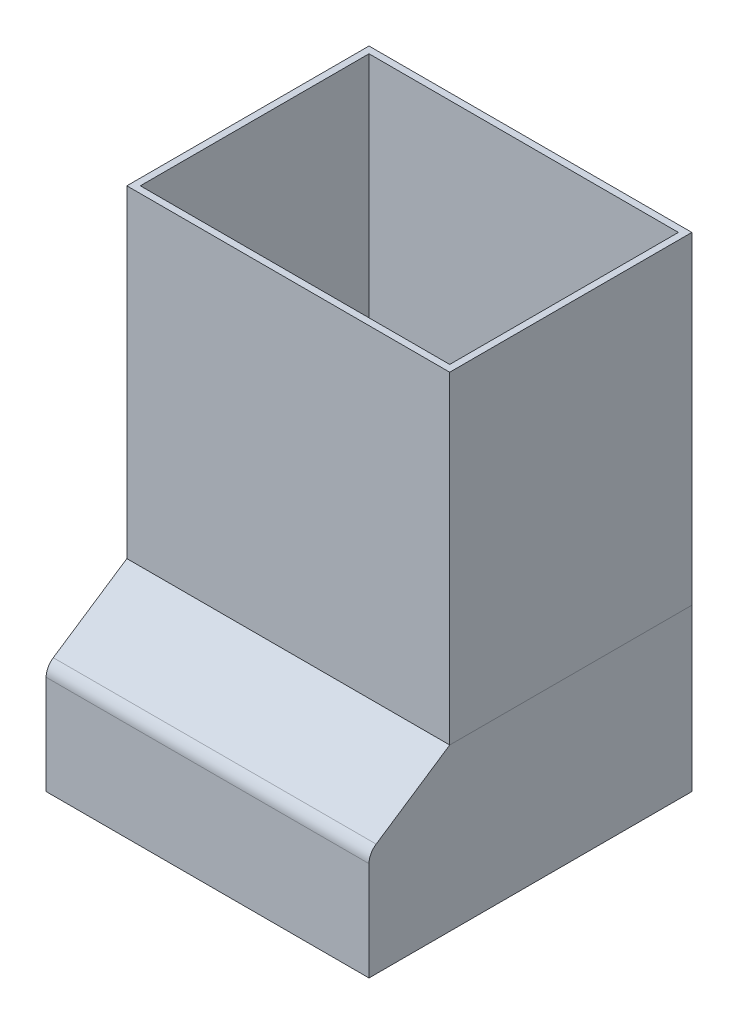
SolidWorks part; units mm, degrees
ref_plane "Front Plane" through (0, 0, 0) normal (0, 0, 1) x (1, 0, 0)
ref_plane "Top Plane" through (0, 0, 0) normal (0, 1, 0) x (1, 0, 0)
ref_plane "Right Plane" through (0, 0, 0) normal (1, 0, 0) x (0, 0, -1)
sketch "Sketch1" plane through (0, 0, 0) normal (0, 1, 0) x (1, 0, 0)
  line L0 (-304.8, 0) -> (304.8, 0) construction
  line L1 (-304.8, 304.8) -> (304.8, 304.8)
  line L2 (-304.8, 304.8) -> (-304.8, -304.8)
  line L3 (-304.8, -304.8) -> (304.8, -304.8)
  line L4 (304.8, 304.8) -> (304.8, -304.8)
  line L5 (-304.8, -304.8) -> (304.8, -304.8) construction
  point P6 (0, 0)
  point P7 (-260.9278, -304.8)
  dimension "D1" = 609.6
  dimension "D2" = 609.6
extrude "Boss-Extrude1" add sketch "Sketch1" along normal blind 304.8 contours L2 L1 L4 L3
sketch "Sketch9" plane through (0, 304.8, 0) normal (0, 1, 0) x (1, 0, 0)
  line L0 (-304.8, -152.4) -> (304.8, -152.4) construction
  line L1 (-304.8, 304.8) -> (-304.8, -304.8) construction
  line L2 (304.8, 304.8) -> (304.8, -304.8) construction
  line L3 (-304.8, -304.8) -> (304.8, -304.8) construction
  dimension "D1" = 152.4
sketch "Sketch10" plane through (0, 0, 304.8) normal (0, 0, 1) x (1, 0, 0)
  line L0 (-304.8, 203.2) -> (304.8, 203.2) construction
  line L1 (-304.8, 304.8) -> (-304.8, 0) construction
  line L2 (304.8, 304.8) -> (304.8, 0) construction
  line L3 (-304.8, 0) -> (304.8, 0) construction
  dimension "D1" = 203.2
sketch "Sketch11" plane through (304.8, 0, 0) normal (1, 0, 0) x (0, 0, -1)
  line L0 (-304.8, 203.2) -> (-152.4, 304.8)
extrude "Cut-Extrude2" cut sketch "Sketch11" against normal blind 609.6 and the other way through all contours L0
shell "Shell11" thickness 12.7
sketch "Sketch13" plane through (0, 304.8, 0) normal (0, 1, 0) x (1, 0, 0)
  line L0 (-304.8, 304.8) -> (-304.8, -152.4)
  line L1 (-304.8, -152.4) -> (304.8, -152.4)
  line L2 (304.8, -152.4) -> (304.8, 304.8)
  line L3 (304.8, 304.8) -> (-304.8, 304.8)
extrude "Boss-Extrude7" add sketch "Sketch13" along normal blind 609.6 separate body
shell "Shell13" thickness 12.7 removed face at (0, 914.4, -76.2)
sketch "Sketch14" plane through (0, 317.5, 0) normal (0, 1, 0) x (1, 0, 0)
  line L0 (-292.1, -38.1) -> (-165.1, -38.1)
  line L1 (-292.1, 292.1) -> (-292.1, -139.7) construction
  line L2 (-165.1, -38.1) -> (-165.1, -139.7)
  line L3 (-292.1, -139.7) -> (292.1, -139.7) construction
  line L4 (-165.1, -139.7) -> (-292.1, -139.7)
  line L5 (-292.1, -139.7) -> (-292.1, -38.1)
  dimension "D1" = 127
  dimension "D2" = 101.6
extrude "Boss-Extrude8" add sketch "Sketch14" along normal blind 152.4
shell "Shell14" thickness 12.7 removed face at (-228.6, 469.9, 88.9)
sketch "Sketch17" plane through (0, 317.5, 0) normal (0, 1, 0) x (1, 0, 0)
  line L1 (-292.1, -50.8) -> (-177.8, -50.8)
  line L2 (-292.1, -50.8) -> (-292.1, -139.7)
  line L3 (-292.1, -139.7) -> (-177.8, -139.7)
  line L4 (-177.8, -50.8) -> (-177.8, -139.7)
  point P0 (-177.8, -50.8)
extrude "Cut-Extrude3" cut sketch "Sketch17" against normal blind 237.744
fillet "Fillet2" radius 30.32 1 edges at (0, 203.2, 304.8)
